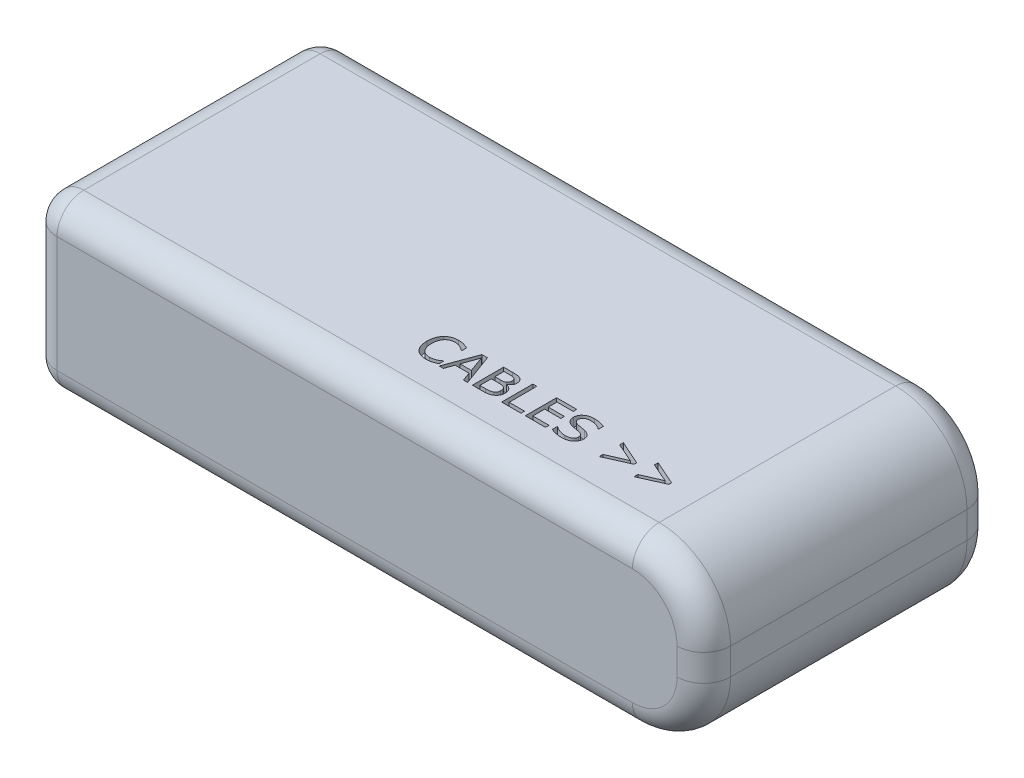
SolidWorks part; units mm, degrees
ref_plane "Front Plane" through (0, 0, 0) normal (0, 0, 1) x (1, 0, 0)
ref_plane "Top Plane" through (0, 0, 0) normal (0, 1, 0) x (1, 0, 0)
ref_plane "Right Plane" through (0, 0, 0) normal (1, 0, 0) x (0, 0, -1)
sketch "Sketch1" plane through (0, 0, 0) normal (0, 1, 0) x (1, 0, 0)
  line L1 (0, 0) -> (75.5, 0)
  line L2 (0, 0) -> (0, 32.5)
  line L3 (0, 32.5) -> (75.5, 32.5)
  line L4 (75.5, 0) -> (75.5, 32.5)
  dimension "D1" = 32.5
  dimension "D2" = 75.5
extrude "Boss-Extrude1" add sketch "Sketch1" along normal blind 19
fillet "Fillet2" radius 3 10 edges at (0, 9.5, -32.5) (0, 19, -16.25) (0, 9.5, 0) (0, 0, -16.25) (75.5, 9.5, -32.5) (75.5, 9.5, 0) (37.75, 0, -32.5) (37.75, 19, -32.5) (37.75, 0, 0) (37.75, 19, 0)
fillet "Fillet3" radius 8 6 edges at (74.6213, 0.8787, -31.6213) (74.6213, 0.8787, -0.8787) (74.6213, 18.1213, -31.6213) (74.6213, 18.1213, -0.8787) (75.5, 19, -16.25) (75.5, 0, -16.25)
sketch "Sketch4" plane through (0, 19, 0) normal (0, 1, 0) x (1, 0, 0)
  text T0 "CABLES >>" font "Verdana" height 3.5
extrude "Cut-Extrude1" cut sketch "Sketch4" against normal blind 1
